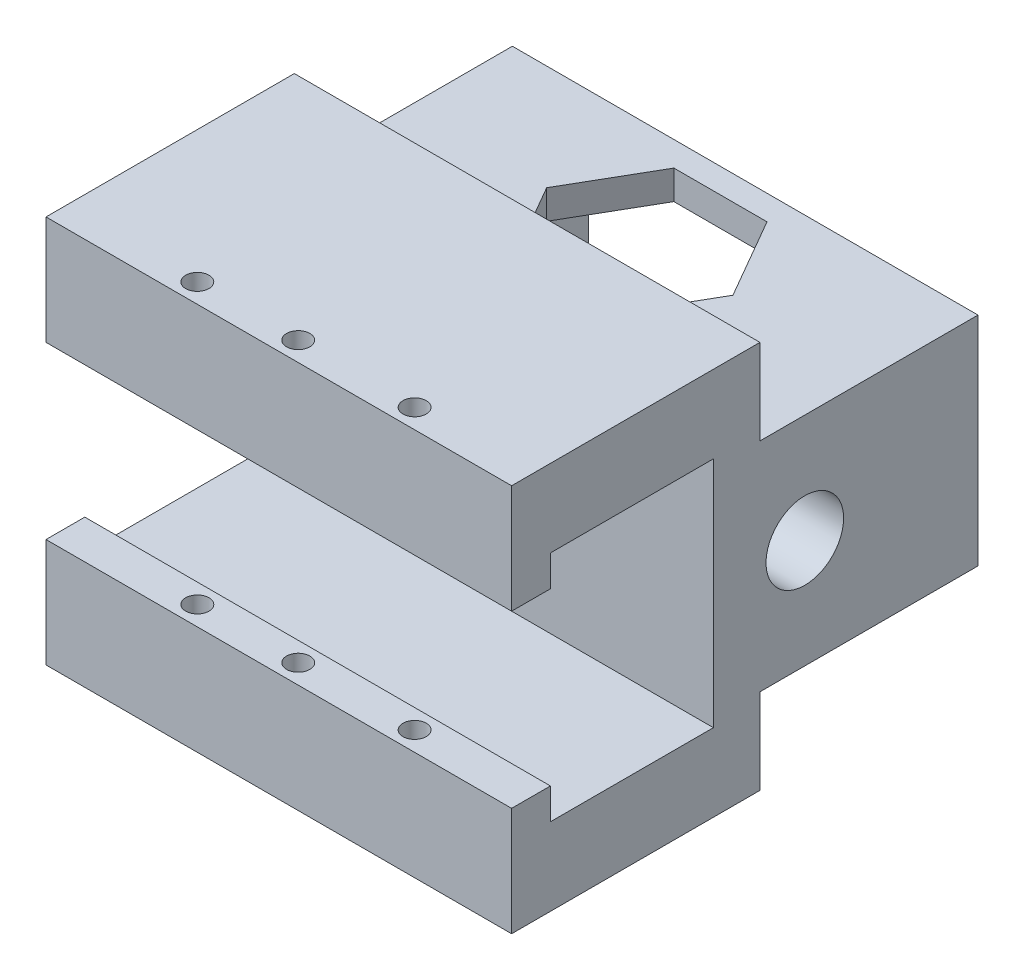
SolidWorks part; units mm, degrees
ref_plane "前视基准面" through (0, 0, 0) normal (0, 0, 1) x (1, 0, 0)
ref_plane "上视基准面" through (0, 0, 0) normal (0, 1, 0) x (1, 0, 0)
ref_plane "右视基准面" through (0, 0, 0) normal (1, 0, 0) x (0, 0, -1)
sketch "草图1" plane through (0, 0, 0) normal (0, 0, 1) x (1, 0, 0)
  line L1 (30, -25) -> (-30, -25)
  line L2 (30, -25) -> (30, 25)
  line L3 (30, 25) -> (-30, 25)
  line L4 (-30, -25) -> (-30, 25)
  line L5 (30, -25) -> (-30, 25) construction
  line L6 (30, 25) -> (-30, -25) construction
  point P0 (0, 0)
  dimension "D1" = 50
  dimension "D2" = 60
extrude "凸台-拉伸1" add sketch "草图1" along normal blind 6
sketch "草图2" plane through (0, 0, 6) normal (0, 0, 1) x (1, 0, 0)
  line L0 (30, -25) -> (30, 25) construction
  line L1 (-30, 25) -> (30, 25)
  line L2 (-30, 25) -> (-30, 15)
  line L3 (-30, 15) -> (30, 15)
  line L4 (30, 25) -> (30, 15)
  line L6 (-30, -25) -> (30, -25)
  line L7 (-30, -25) -> (-30, -15)
  line L8 (-30, -15) -> (30, -15)
  line L9 (30, -25) -> (30, -15)
  dimension "D1" = 10
  dimension "D2" = 10
extrude "凸台-拉伸3" add sketch "草图2" along normal blind 26
sketch "草图3" plane through (0, -15, 0) normal (0, 1, 0) x (1, 0, 0)
  line L0 (30, -32) -> (30, -6) construction
  line L1 (-30, -32) -> (30, -32)
  line L2 (-30, -32) -> (-30, -27)
  line L3 (-30, -27) -> (30, -27)
  line L4 (30, -32) -> (30, -27)
  dimension "D1" = 5
extrude "凸台-拉伸4" add sketch "草图3" along normal blind 4
sketch "草图4" plane through (0, 15, 0) normal (0, -1, 0) x (1, 0, 0)
  line L0 (30, 32) -> (30, 6) construction
  line L1 (-30, 32) -> (30, 32)
  line L2 (-30, 32) -> (-30, 27)
  line L3 (-30, 27) -> (30, 27)
  line L4 (30, 32) -> (30, 27)
  dimension "D1" = 5
extrude "凸台-拉伸5" add sketch "草图4" along normal blind 4
sketch "草图9" plane through (0, 0, 0) normal (0, 0, -1) x (-1, 0, 0)
  line L1 (20.2, -10.25) -> (-20.2, -10.25)
  line L2 (20.2, -10.25) -> (20.2, 10.25)
  line L3 (20.2, 10.25) -> (-20.2, 10.25)
  line L4 (-20.2, -10.25) -> (-20.2, 10.25)
  line L5 (20.2, -10.25) -> (-20.2, 10.25) construction
  line L6 (20.2, 10.25) -> (-20.2, -10.25) construction
  line L7 (30, -14) -> (-30, -14)
  line L8 (30, -14) -> (30, 14)
  line L9 (30, 14) -> (-30, 14)
  line L10 (-30, -14) -> (-30, 14)
  line L11 (30, -14) -> (-30, 14) construction
  line L12 (30, 14) -> (-30, -14) construction
  point P0 (0, 0)
  point P5 (0, 0)
  dimension "D1" = 20.5
  dimension "D2" = 40.4
  dimension "D3" = 28
  dimension "D4" = 60
extrude "凸台-拉伸6" add sketch "草图9" along normal blind 28.1
sketch "草图11" plane through (30, 0, 0) normal (1, 0, 0) x (0, 0, -1)
  circle A0 centre (5.7817, 0) radius 5
  dimension "D1" = 10
extrude "切除-拉伸3" cut sketch "草图11" against normal blind 10
sketch "草图12" plane through (0, 0, -28.1) normal (0, 0, -1) x (-1, 0, 0)
  circle A0 centre (24.8, -5) radius 2.25
  circle A1 centre (24.8, 5) radius 2.25
  circle A2 centre (-24.8, -5) radius 2.25
  circle A3 centre (-24.8, 5) radius 2.25
extrude "切除-拉伸4" cut sketch "草图12" against normal blind 16
sketch "草图13" plane through (0, 14, 0) normal (0, 1, 0) x (1, 0, 0)
  line L1 (-12, 14.5188) -> (-6, 4.1265)
  line L2 (-6, 4.1265) -> (6, 4.1265)
  line L3 (6, 4.1265) -> (12, 14.5188)
  line L4 (12, 14.5188) -> (6, 24.9111)
  line L5 (6, 24.9111) -> (-6, 24.9111)
  line L6 (-6, 24.9111) -> (-12, 14.5188)
  circle A0 centre (0, 14.5188) radius 10.3923 construction
  dimension "D1" = 12
extrude "切除-拉伸5" cut sketch "草图13" against normal through all
sketch "草图15" plane through (0, -11, 0) normal (0, 1, 0) x (1, 0, 0)
  circle A0 centre (15, -29.5) radius 1.5
  circle A1 centre (0, -29.5) radius 1.5
  circle A2 centre (-13, -29.5) radius 1.5
sketch "草图16" plane through (0, 11, 0) normal (0, -1, 0) x (1, 0, 0)
  circle A0 centre (-13, 29.5) radius 1.5
  circle A1 centre (0, 29.5) radius 1.5
  circle A2 centre (15, 29.5) radius 1.5
extrude "切除-拉伸6" cut sketch "草图15" against normal through all
extrude "切除-拉伸7" cut sketch "草图16" against normal through all
